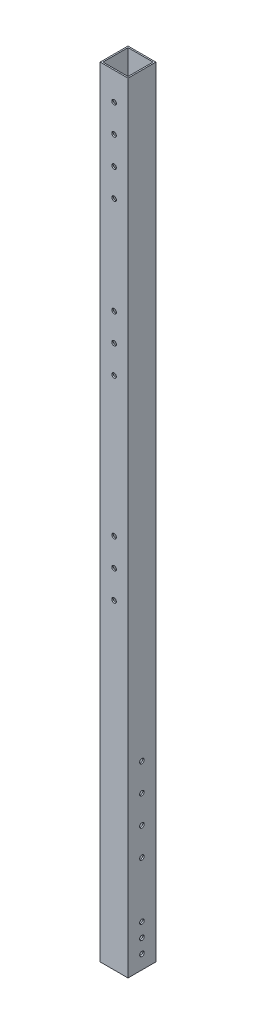
SolidWorks part; units mm, degrees
ref_plane "前视基准面" through (0, 0, 0) normal (0, 0, 1) x (1, 0, 0)
ref_plane "上视基准面" through (0, 0, 0) normal (0, 1, 0) x (1, 0, 0)
ref_plane "右视基准面" through (0, 0, 0) normal (1, 0, 0) x (0, 0, -1)
other "Configuration Table"
sketch "草图1" plane through (0, 0, 0) normal (0, 1, 0) x (1, 0, 0)
  line L9 (-9, 9) -> (9, 9)
  line L10 (-9, 9) -> (-9, -9)
  line L11 (-9, -9) -> (9, -9)
  line L12 (9, 9) -> (9, -9)
  line L13 (-9, 9) -> (9, -9) construction
  line L14 (-9, -9) -> (9, 9) construction
  line L15 (-10, 10) -> (10, 10)
  line L16 (-10, 10) -> (-10, -10)
  line L17 (-10, -10) -> (10, -10)
  line L18 (10, 10) -> (10, -10)
  line L19 (-10, 10) -> (10, -10) construction
  line L20 (-10, -10) -> (10, 10) construction
  point P0 (0, 0)
  point P6 (0, 0)
  dimension "D1" = 18
  dimension "D2" = 18
  dimension "D3" = 20
  dimension "D4" = 20
extrude "凸台-拉伸1" add sketch "草图1" along normal blind 740
sketch "草图3" plane through (0, 0, 10) normal (0, 0, 1) x (1, 0, 0)
  line L0 (0, 740) -> (0, 720) construction
  line L1 (-10, 740) -> (10, 740) construction
  line L2 (0, 720) -> (0, 700) construction
  line L3 (0, 700) -> (0, 680) construction
  line L4 (0, 680) -> (0, 660) construction
  circle A0 centre (0, 720) radius 1.65
  circle A1 centre (0, 700) radius 1.65
  circle A2 centre (0, 680) radius 1.65
  circle A3 centre (0, 660) radius 1.65
  circle A4 centre (0, 590) radius 1.65
  circle A5 centre (0, 570) radius 1.65
  circle A6 centre (0, 550) radius 1.65
  circle A7 centre (0, 450) radius 1.65
  circle A8 centre (0, 430) radius 1.65
  circle A9 centre (0, 410) radius 1.65
  dimension "D5" = 3.3
  dimension "D6" = 3.3
  dimension "D7" = 3.3
  dimension "D8" = 3.3
  dimension "D10" = 3.3
  dimension "D11" = 3.3
  dimension "D14" = 3.3
  dimension "D18" = 3.3
  dimension "D19" = 3.3
  dimension "D20" = 3.3
  dimension "D1" = 20
  dimension "D2" = 20
  dimension "D3" = 20
  dimension "D4" = 20
  dimension "D9" = 150
  dimension "D12" = 20
  dimension "D13" = 20
  dimension "D15" = 20
  dimension "D16" = 20
  dimension "D17" = 100
extrude "切除-拉伸1" cut sketch "草图3" against normal blind 32
sketch "草图4" plane through (10, 0, 0) normal (1, 0, 0) x (0, 0, -1)
  line L0 (0, 0) -> (0, 250) construction
  circle A0 centre (0, 250) radius 1.65
  circle A1 centre (0, 270) radius 1.65
  circle A2 centre (0, 290) radius 1.65
  circle A3 centre (0, 310) radius 1.65
  dimension "D2" = 3.3
  dimension "D1" = 250
  dimension "D3" = 4
extrude "切除-拉伸2" cut sketch "草图4" against normal through all
sketch "草图5" plane through (0, 0, 0) normal (0, -1, 0) x (1, 0, 0)
  circle A0 centre (0, 0) radius 14.5662
extrude "切除-拉伸3" cut sketch "草图5" against normal blind 180
sketch "草图6" plane through (10, 0, 0) normal (1, 0, 0) x (0, 0, -1)
  circle A0 centre (0, 190) radius 1.65
  circle A1 centre (0, 200) radius 1.65
  circle A2 centre (0, 210) radius 1.65
  dimension "D1" = 3.3
  dimension "D2" = 3
extrude "切除-拉伸4" cut sketch "草图6" against normal blind 30
